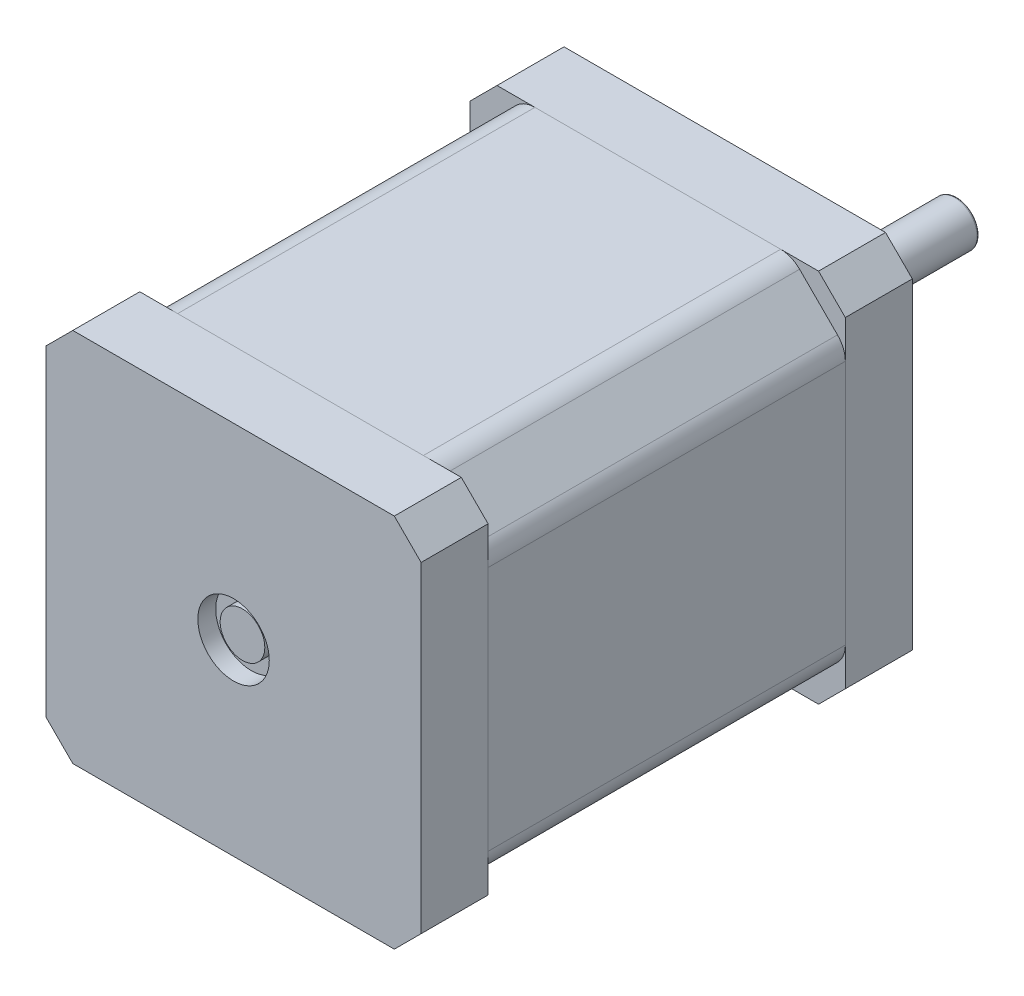
SolidWorks part; units mm, degrees
ref_plane "Ön Düzlem" through (0, 0, 0) normal (0, 0, 1) x (1, 0, 0)
ref_plane "Üst Düzlem" through (0, 0, 0) normal (0, 1, 0) x (1, 0, 0)
ref_plane "Sağ Düzlem" through (0, 0, 0) normal (1, 0, 0) x (0, 0, -1)
sketch "Çizim1" plane through (0, 0, 0) normal (0, 0, 1) x (1, 0, 0)
  line L0 (-15.8783, 20.121) -> (-20.121, 15.8783)
  line L1 (20.121, 15.8783) -> (15.8783, 20.121)
  line L2 (20.121, -15.8783) -> (15.8783, -20.121)
  line L3 (-15.8783, -20.121) -> (-20.121, -15.8783)
  line L4 (13.757, -20.9997) -> (-13.757, -20.9997)
  line L5 (20.9997, -13.757) -> (20.9997, 13.757)
  line L6 (13.757, 20.9997) -> (-13.757, 20.9997)
  line L7 (-20.9997, -13.757) -> (-20.9997, 13.757)
  line L9 (-15.5, -15.5) -> (15.5, -15.5) construction
  line L10 (-15.5, -15.5) -> (-15.5, 15.5) construction
  line L11 (-15.5, 15.5) -> (15.5, 15.5) construction
  line L12 (15.5, -15.5) -> (15.5, 15.5) construction
  line L13 (-15.5, -15.5) -> (15.5, 15.5) construction
  line L14 (-15.5, 15.5) -> (15.5, -15.5) construction
  arc A0 (-20.9997, 13.757) -> (-20.121, 15.8783) centre (-17.9997, 13.757) cw
  arc A1 (-15.8783, 20.121) -> (-13.757, 20.9997) centre (-13.757, 17.9997) cw
  arc A2 (13.757, 20.9997) -> (15.8783, 20.121) centre (13.757, 17.9997) cw
  arc A3 (20.121, 15.8783) -> (20.9997, 13.757) centre (17.9997, 13.757) cw
  arc A4 (20.9997, -13.757) -> (20.121, -15.8783) centre (17.9997, -13.757) cw
  arc A5 (15.8783, -20.121) -> (13.757, -20.9997) centre (13.757, -17.9997) cw
  arc A6 (-13.757, -20.9997) -> (-15.8783, -20.121) centre (-13.757, -17.9997) cw
  arc A7 (-20.121, -15.8783) -> (-20.9997, -13.757) centre (-17.9997, -13.757) cw
  circle A8 centre (-15.5, 15.5) radius 1.5
  circle A9 centre (15.5, 15.5) radius 1.5
  circle A10 centre (15.5, -15.5) radius 1.5
  circle A11 centre (-15.5, -15.5) radius 1.5
  point P6 (0, 0)
  point P28 (0, 20.9997)
  point P29 (0, -20.9997)
  dimension "D1" = 3
  dimension "D2" = 3
  dimension "D3" = 41.9993
  dimension "D7" = 3
  dimension "D8" = 3
  dimension "D9" = 3
  dimension "D10" = 3
  dimension "D4" = 41.9993
  dimension "D5" = 31
  dimension "D6" = 31
extrude "Yükseklik-Ekstrüzyon1" add sketch "Çizim1" along normal blind 40
sketch "Çizim2" plane through (0, 0, 0) normal (0, 0, -1) x (-1, 0, 0)
  line L0 (-21, 18) -> (-18, 21)
  line L1 (-18, -21) -> (18, -21)
  line L2 (-21, -18) -> (-21, 18)
  line L3 (-18, 21) -> (18, 21)
  line L4 (21, -18) -> (21, 18)
  line L5 (-21, -21) -> (21, 21) construction
  line L6 (-21, 21) -> (21, -21) construction
  line L7 (18, 21) -> (21, 18)
  line L8 (18, -21) -> (21, -18)
  line L9 (-21, -18) -> (-18, -21)
  circle A0 centre (-15.5, 15.5) radius 1.5
  circle A1 centre (15.5, 15.5) radius 1.5
  circle A2 centre (15.5, -15.5) radius 1.5
  circle A3 centre (-15.5, -15.5) radius 1.5
  point P0 (0, 0)
  dimension "D1" = 42
  dimension "D2" = 42
extrude "Yükseklik-Ekstrüzyon2" add sketch "Çizim2" along normal blind 7.5
sketch "Çizim3" plane through (0, 0, -7.5) normal (0, 0, -1) x (-1, 0, 0)
  circle A0 centre (0, 0) radius 11
  dimension "D1" = 22
extrude "Yükseklik-Ekstrüzyon3" add sketch "Çizim3" along normal blind 2
fillet "Radyus1" radius 1 1 edges at (11, 0, -7.5)
sketch "Çizim4" plane through (0, 0, -9.5) normal (0, 0, -1) x (-1, 0, 0)
  circle A0 centre (0, 0) radius 4
  dimension "D1" = 8
extrude "Kes-Ekstrüzyon2" cut sketch "Çizim4" against normal blind 2
sketch "Çizim5" plane through (0, 0, -7.5) normal (0, 0, -1) x (-1, 0, 0)
  circle A0 centre (0, 0) radius 2.5
  dimension "D1" = 5
extrude "Yükseklik-Ekstrüzyon4" add sketch "Çizim5" along normal blind 26
sketch "Çizim6" plane through (0, 0, -33.5) normal (0, 0, -1) x (-1, 0, 0)
  line L0 (-2.5, 0) -> (2, 0) construction
  line L1 (2, 2.1161) -> (2, -2.5)
  line L2 (2, -2.5) -> (3.2331, -2.5)
  line L3 (3.2331, -2.5) -> (3.2331, 2.1161)
  line L4 (3.2331, 2.1161) -> (2, 2.1161)
  circle A0 centre (0, 0) radius 2.5 construction
  circle A1 centre (0, 0) radius 2.5 construction
  dimension "D1" = 4.5
extrude "Kes-Ekstrüzyon3" cut sketch "Çizim6" against normal blind 17
fillet "Radyus2" radius 0.25 2 edges at (-2, 0, -33.5) (2.5, 0, -33.5)
sketch "Çizim7" plane through (0, 0, 40) normal (0, 0, 1) x (1, 0, 0)
  line L16 (-18, 21) -> (18, 21)
  line L17 (18, 21) -> (21, 18)
  line L18 (21, 18) -> (21, -18)
  line L19 (21, -18) -> (18, -21)
  line L20 (18, -21) -> (-18, -21)
  line L21 (-18, -21) -> (-21, -18)
  line L22 (-21, -18) -> (-21, 18)
  line L23 (-21, 18) -> (-18, 21)
extrude "Yükseklik-Ekstrüzyon5" add sketch "Çizim7" along normal blind 7.5
sketch "Çizim8" plane through (0, 0, 47.5) normal (0, 0, 1) x (1, 0, 0)
  circle A0 centre (0, 0) radius 4
  dimension "D1" = 8
extrude "Kes-Ekstrüzyon4" cut sketch "Çizim8" against normal blind 2
sketch "Çizim10" plane through (0, 0, 45.5) normal (0, 0, 1) x (1, 0, 0)
  circle A0 centre (0, 0) radius 2.5
  dimension "D1" = 5
extrude "Yükseklik-Ekstrüzyon7" add sketch "Çizim10" along normal blind 1
sketch "Çizim11" plane through (-20.9997, 0, 0) normal (-1, 0, 0) x (0, 0, 1)
  line L0 (12, 0) -> (-12, 0) construction
  line L1 (19, -10) -> (5, -10)
  line L2 (19, -10) -> (19, 10)
  line L3 (19, 10) -> (5, 10)
  line L4 (5, -10) -> (5, 10)
  line L5 (19, -10) -> (5, 10) construction
  line L6 (19, 10) -> (5, -10) construction
  line L7 (40, 13.757) -> (40, -13.757) construction
  point P0 (12, 0)
  dimension "D1" = 14
  dimension "D2" = 20
  dimension "D3" = 21
split line "Ayrım Çizgisi2"
sketch "Çizim12" plane through (-20.9997, 0, 0) normal (-1, 0, 0) x (0, 0, 1)
  line L0 (7.6653, -10) -> (7.6653, 10) construction
  line L1 (5, -10) -> (19, -10) construction
  line L2 (19, 10) -> (5, 10) construction
  text T0 "STEPPING MOTOR\r\nModel No: 17HS4401\r\nLot No:2017411\r\n17A  0.42N.M" font "Century Gothic" height in points 5
extrude "Yükseklik-Ekstrüzyon8" add sketch "Çizim12" along normal blind 0.1
